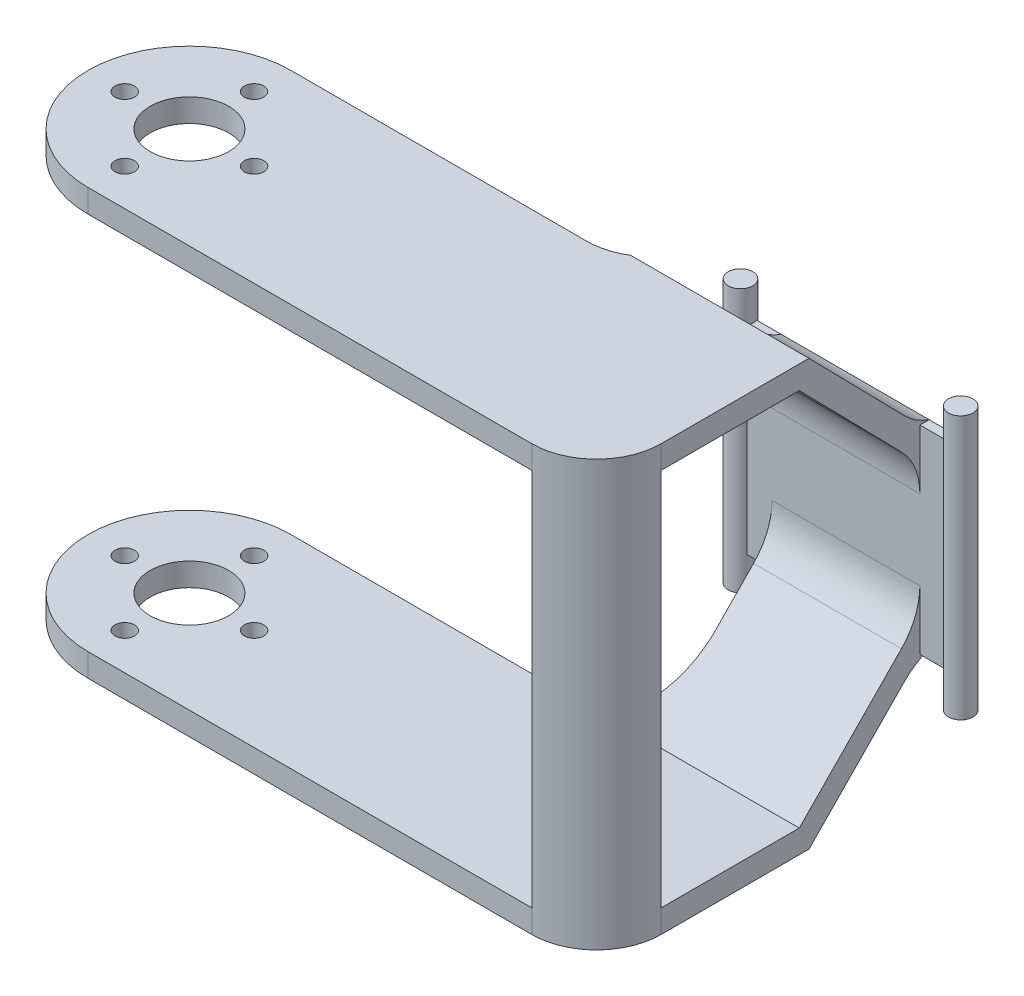
SolidWorks part; units mm, degrees
ref_plane "Front Plane" through (0, 0, 0) normal (0, 0, 1) x (1, 0, 0)
ref_plane "Top Plane" through (0, 0, 0) normal (0, 1, 0) x (1, 0, 0)
ref_plane "Right Plane" through (0, 0, 0) normal (1, 0, 0) x (0, 0, -1)
sketch "Sketch1" plane through (0, 0, 0) normal (0, 1, 0) x (1, 0, 0)
  line L1 (11.915, 0.5) -> (-11.915, 0.5)
  line L2 (11.915, 0.5) -> (11.915, -0.5)
  line L3 (11.915, -0.5) -> (-11.915, -0.5)
  line L4 (-11.915, 0.5) -> (-11.915, -0.5)
  line L5 (11.915, 0.5) -> (-11.915, -0.5) construction
  line L6 (11.915, -0.5) -> (-11.915, 0.5) construction
  point P0 (0, 0)
  dimension "D1" = 23.83
  dimension "D3" = 1
extrude "Boss-Extrude1" add sketch "Sketch1" along normal blind 21.5
ref_plane "Plane1" through (0, 10.75, 0) normal (0, 1, 0) x (1, 0, 0)
sketch "Sketch2" plane through (0, 10.75, 0) normal (0, 1, 0) x (1, 0, 0)
  line L0 (11.915, -0.5) -> (11.915, 0.5) construction
  line L1 (-11.915, 0.5) -> (-11.915, -0.5) construction
  line L2 (11.915, -0.5) -> (11.915, 0.5) construction
  line L3 (-11.915, 0.5) -> (-11.915, -0.5) construction
  circle A0 centre (-11.915, 0) radius 1.325
  circle A1 centre (11.915, 0) radius 1.325
  dimension "D1" = 2.65
extrude "Boss-Extrude2" add sketch "Sketch2" along normal mid plane 28.5
sketch "Sketch3" plane through (0, 21.5, 0) normal (0, 1, 0) x (1, 0, 0)
  line L0 (-10.688, -0.5) -> (10.688, -0.5) construction
  line L1 (-7.5, -0.5) -> (7.5, -0.5)
  line L2 (-7.5, -0.5) -> (-7.5, -26.5)
  line L3 (-7.5, -26.5) -> (7.5, -26.5)
  line L4 (7.5, -0.5) -> (7.5, -26.5)
  line L5 (0, -1000) -> (0, 49000) construction
  line L6 (-7.5, -26.5) -> (-32.5, -26.5)
  line L7 (-7.5, -26.5) -> (-7.5, -3.5)
  line L8 (-7.5, -3.5) -> (-32.5, -3.5)
  line L9 (-32.5, -26.5) -> (-32.5, -3.5)
  line L11 (-4.5, -3.5) -> (4.5, -3.5)
  line L12 (4.5, -3.5) -> (4.5, -23.5)
  line L13 (-4.5, -23.5) -> (4.5, -23.5)
  line L14 (-10.5, -23.5) -> (-29.5, -23.5)
  line L16 (-10.5, -6.5) -> (-29.5, -6.5)
  line L18 (-29.5, -23.5) -> (-29.5, -6.5) construction
  line L19 (-10.5, -23.5) -> (-10.5, -6.5) construction
  line L20 (-4.5, -3.5) -> (-4.5, -23.5) construction
  line L21 (-4.5, -3.5) -> (-4.5, -6.5)
  line L22 (-4.5, -6.5) -> (-10.5, -6.5)
  line L23 (-4.5, -23.5) -> (-10.5, -23.5)
  line L24 (-18.5, -6.5) -> (-18.5, -23.5)
  circle A0 centre (-32.5, -15) radius 11.5
  circle A1 centre (-32.5, -15) radius 4.25
  circle A2 centre (-32.5, -15) radius 7 construction
  circle A3 centre (-32.5, -8) radius 1.05
  circle A4 centre (-25.5, -15) radius 1.05
  circle A5 centre (-32.5, -22) radius 1.05
  circle A6 centre (-39.5, -15) radius 1.05
  point P10 (0, -0.5)
  line M14 (-10.688, -0.5) -> (10.688, -0.5)
  dimension "D5" = 8.5
  dimension "D6" = 14
  dimension "D7" = 2.1
  dimension "D1" = 15
  dimension "D2" = 26
  dimension "D3" = 23
  dimension "D4" = 25
  dimension "D9" = 14
  dimension "D8" = 3
extrude "Boss-Extrude3" [suppressed] add sketch "Sketch3" against normal up to surface (18.5 mm away) contours L4 L2 L3 M14 | A0 L6 L2 L8 | A5 L9 A0 A3 A1 A4 | A5 L9 A1 A3 A0 A6 | A0 L16 L22 L2 L8 | A0 L6 L2 L23 L14
sketch "Sketch4" plane through (0, 0, 0) normal (1, 0, 0) x (0, 0, -1)
  line L0 (-0.5, 21.5) -> (-12.5, 33.75)
  line L1 (-12.5, 33.75) -> (-35.5, 33.75)
  line L2 (-35.5, 33.75) -> (-35.5, 31.25)
  line L3 (-35.5, 31.25) -> (-13.5507, 31.25)
  line L4 (-13.5507, 31.25) -> (-0.5, 17.9274)
  line L5 (-0.5, 21.5) -> (-0.5, 0) construction
  line L6 (-0.5, 21.5) -> (-0.5, 0)
  line L7 (-0.5, 0) -> (-12.5, -12.25)
  line L8 (-12.5, -12.25) -> (-35.5, -12.25)
  line L9 (-35.5, -12.25) -> (-35.5, -9.75)
  line L10 (-35.5, -9.75) -> (-13.5507, -9.75)
  line L11 (-13.5507, -9.75) -> (-0.5, 3.5726)
  line L12 (-1000.5, 10.75) -> (48999.5, 10.75) construction
  line L13 (-35.5, 31.25) -> (-35.5, -9.75) construction
  point P3 (-35.5, 10.75)
  point P20 (-0.5, 10.75)
  dimension "D1" = 2.5
  dimension "D2" = 41
  dimension "D3" = 23
  dimension "D4" = 2.5
  dimension "D5" = 35
  dimension "D6" = 2.5
extrude "Boss-Extrude4" add sketch "Sketch4" along normal mid plane 16 contours L6 L0 L1 L2 L3 L4 | L11 L10 L9 L8 L7 L6
sketch "Sketch5" plane through (-8, 0, 0) normal (-1, 0, 0) x (0, 0, 1)
  line L1 (35.5, 33.75) -> (13.5507, 33.75)
  line L2 (35.5, 33.75) -> (35.5, 31.25)
  line L3 (35.5, 31.25) -> (13.5507, 31.25)
  line L4 (13.5507, 33.75) -> (13.5507, 31.25)
  line L5 (35.5, -12.25) -> (13.5507, -12.25)
  line L6 (35.5, -12.25) -> (35.5, -9.75)
  line L7 (35.5, -9.75) -> (13.5507, -9.75)
  line L8 (13.5507, -12.25) -> (13.5507, -9.75)
extrude "Boss-Extrude5" add sketch "Sketch5" along normal blind 50
sketch "Sketch6" plane through (0, 33.75, 0) normal (0, 1, 0) x (1, 0, 0)
  line L0 (-47.0253, -13.5507) -> (-47.0253, -35.5) construction
  line L1 (-58, -13.5507) -> (-8, -13.5507) construction
  line L2 (8, -35.5) -> (-58, -35.5) construction
  line L3 (-58, -24.5253) -> (8, -24.5253) construction
  line L4 (-58, -35.5) -> (-58, -13.5507) construction
  line L5 (8, -12.5) -> (8, -35.5) construction
  line L6 (-47.0253, -13.5507) -> (-58, -13.5507)
  line L7 (-58, -13.5507) -> (-58, -35.5)
  line L8 (-58, -35.5) -> (-47.0253, -35.5)
  circle A0 centre (-47.0253, -24.5253) radius 10.9747
  circle A1 centre (-47.0253, -24.5253) radius 4.25
  circle A2 centre (-47.0253, -24.5253) radius 7 construction
  circle A3 centre (-47.0253, -17.5253) radius 1.05
  circle A4 centre (-40.0253, -24.5253) radius 1.05
  circle A5 centre (-47.0253, -31.5253) radius 1.05
  circle A6 centre (-54.0253, -24.5253) radius 1.05
  point P12 (-47.0253, -24.5253)
  line M9 (-8, -13.5507) -> (-58, -13.5507)
  line M10 (-58, -13.5507) -> (-58, -35.5)
  line M11 (-58, -35.5) -> (8, -35.5)
  dimension "D1" = 8.5
  dimension "D2" = 14
  dimension "D3" = 2.1
extrude "Cut-Extrude1" cut sketch "Sketch6" against normal through all contours A1 | A6 | A3 | A4 | A5 | A0 M9 M10 | A0 L7 M11
fillet "Fillet1" radius 7 4 edges at (-8, -11, 13.5507) (-8, 32.5, 13.5507) (8, -11, 35.5) (8, 32.5, 35.5)
fillet "Fillet2" radius 7 2 edges at (0, 3.5726, 0.5) (0, 17.9274, 0.5)
fillet "Fillet3" radius 7 2 edges at (0, 21.5, 0.5) (0, 0, 0.5)
sketch "Sketch8" plane through (0, -9.75, 0) normal (0, 1, 0) x (1, 0, 0)
  line L0 (-47.0253, -13.5507) -> (-15, -13.5507) construction
  line L1 (-47.0253, -13.5507) -> (-15, -13.5507)
  line L2 (8, -28.5) -> (5, -28.5)
  line L3 (1, -35.5) -> (1, -32.5)
  arc A0 (-15, -13.5507) -> (-8, -6.5507) centre (-15, -6.5507) ccw construction
  arc A1 (1, -35.5) -> (8, -28.5) centre (1, -28.5) ccw construction
  arc A2 (-15, -13.5507) -> (-8, -6.5507) centre (-15, -6.5507) ccw
  arc A3 (1, -35.5) -> (8, -28.5) centre (1, -28.5) ccw
  circle A4 centre (-1.5277, -25.9723) radius 7
  arc M10 (1, -35.5) -> (8, -28.5) centre (1, -28.5) ccw
  dimension "D1" = 3
extrude "Boss-Extrude6" add sketch "Sketch8" along normal up to surface (41 mm away) contours A4 L3 L2 M10 up to face at (-47.0253, 31.25, 28.7753)
equation "\"D4@Sketch4\"=\"D1@Sketch4\""
equation "\"D6@Sketch4\"=\"D1@Sketch4\""
